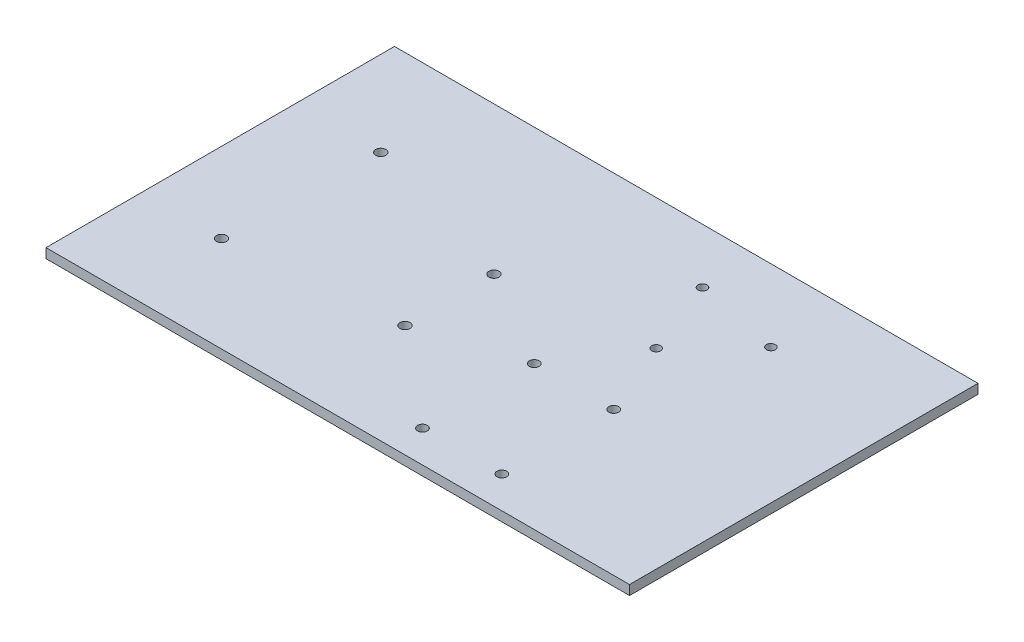
SolidWorks part; units mm, degrees
ref_plane "Front Plane" through (0, 0, 0) normal (0, 0, 1) x (1, 0, 0)
ref_plane "Top Plane" through (0, 0, 0) normal (0, 1, 0) x (1, 0, 0)
ref_plane "Right Plane" through (0, 0, 0) normal (1, 0, 0) x (0, 0, -1)
sketch "Sketch1" plane through (0, 0, 0) normal (0, 1, 0) x (1, 0, 0)
  line L1 (-91.44, 54.61) -> (91.44, 54.61)
  line L2 (-91.44, 54.61) -> (-91.44, -54.61)
  line L3 (-91.44, -54.61) -> (91.44, -54.61)
  line L4 (91.44, 54.61) -> (91.44, -54.61)
  line L5 (-91.44, 54.61) -> (91.44, -54.61) construction
  line L6 (-91.44, -54.61) -> (91.44, 54.61) construction
  point P0 (0, 0)
  dimension "D1" = 182.88
  dimension "D2" = 109.22
extrude "Boss-Extrude1" add sketch "Sketch1" along normal blind 3
sketch "Sketch2" plane through (0, 3, 0) normal (0, 1, 0) x (1, 0, 0)
  line L0 (-91.44, 54.61) -> (-91.44, -54.61) construction
  line L1 (-91.44, -54.61) -> (91.44, -54.61) construction
  line L2 (-66.44, -24.61) -> (-66.44, 28.3) construction
  line L3 (-66.44, -24.61) -> (52.1033, -24.61) construction
  circle A0 centre (-66.44, -24.61) radius 1.6
  circle A1 centre (-64.84, 23.69) radius 1.6
  circle A2 centre (-14.04, 8.39) radius 1.6
  circle A3 centre (-14.04, -19.51) radius 1.6
  dimension "D2" = 30
  dimension "D4" = 3.2
  dimension "D5" = 50.8
  dimension "D6" = 27.9
  dimension "D7" = 5.1
  dimension "D3" = 48.3
  dimension "D1" = 25
extrude "Cut-Extrude1" cut sketch "Sketch2" against normal blind 10
sketch "Sketch3" plane through (0, 3, 0) normal (0, 1, 0) x (1, 0, 0)
  circle A0 centre (31.4921, 13.6895) radius 1.4
  circle A1 centre (22.2303, 37.4695) radius 1.4
  circle A2 centre (49.1763, 31.9775) radius 1.4
  dimension "D1" = 2.8
  dimension "D2" = 18.288
  dimension "D3" = 27.5
  dimension "D4" = 25.52
extrude "Cut-Extrude2" cut sketch "Sketch3" against normal through all
sketch "Sketch4" plane through (0, 3, 0) normal (0, 1, 0) x (1, 0, 0)
  line L0 (16.55, -9.56) -> (41.44, -9.56) construction
  line L1 (16.55, -9.56) -> (16.55, -44.61) construction
  line L2 (41.44, -9.56) -> (41.44, -44.61) construction
  line L3 (91.44, 54.61) -> (-91.44, 54.61) construction
  line L4 (91.44, -54.61) -> (91.44, 54.61) construction
  line L5 (-91.44, -54.61) -> (91.44, -54.61) construction
  circle A0 centre (16.55, -44.61) radius 1.525
  circle A1 centre (41.44, -9.56) radius 1.525
  circle A2 centre (16.55, -9.56) radius 1.525
  circle A3 centre (41.44, -44.61) radius 1.525
  point P0 (60.8847, -8.4778)
  dimension "D1" = 24.89
  dimension "D2" = 35.05
  dimension "D3" = 3.05
  dimension "D4" = 50
  dimension "D5" = 10
extrude "Cut-Extrude3" cut sketch "Sketch4" against normal through all
